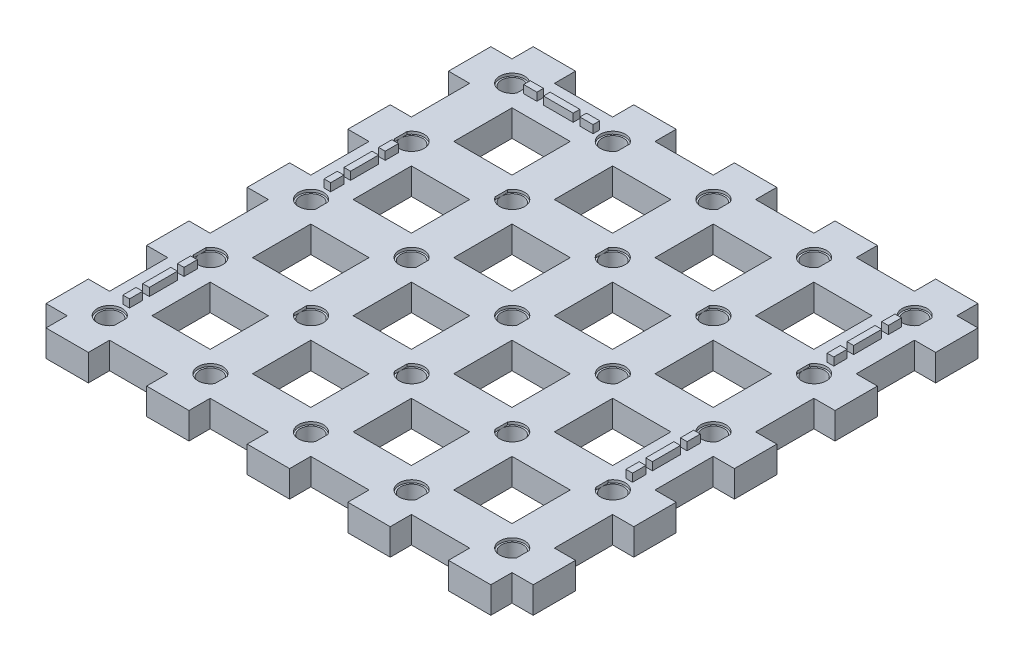
SolidWorks part; units mm, degrees
ref_plane "Front Plane" through (0, 0, 0) normal (0, 0, 1) x (1, 0, 0)
ref_plane "Top Plane" through (0, 0, 0) normal (0, 1, 0) x (1, 0, 0)
ref_plane "Right Plane" through (0, 0, 0) normal (1, 0, 0) x (0, 0, -1)
sketch "Sketch1" plane through (0, 0, 0) normal (0, 1, 0) x (1, 0, 0)
  line L1 (-110, -110) -> (110, -110)
  line L2 (-110, -110) -> (-110, 110)
  line L3 (-110, 110) -> (110, 110)
  line L4 (110, -110) -> (110, 110)
  line L5 (-110, -110) -> (110, 110) construction
  line L6 (-110, 110) -> (110, -110) construction
  point P0 (0, 0)
  dimension "D1" = 220
  dimension "D2" = 220
extrude "Boss-Extrude1" add sketch "Sketch1" along normal blind 10
sketch "Sketch2" plane through (0, 10, 0) normal (0, 1, 0) x (1, 0, 0)
  line L2 (-110, 110) -> (-110, -110) construction
  line L3 (-110, -110) -> (110, -110) construction
  circle A0 centre (-76, -75.925) radius 4.075
  circle A1 centre (-38, -75.925) radius 4.075
  circle A2 centre (0, -75.925) radius 4.075
  circle A3 centre (38, -75.925) radius 4.075
  circle A4 centre (76, -75.925) radius 4.075
  circle A5 centre (-76, -37.925) radius 4.075
  circle A6 centre (-38, -37.925) radius 4.075
  circle A7 centre (0, -37.925) radius 4.075
  circle A8 centre (38, -37.925) radius 4.075
  circle A9 centre (76, -37.925) radius 4.075
  circle A10 centre (-76, 0.075) radius 4.075
  circle A11 centre (-38, 0.075) radius 4.075
  circle A12 centre (0, 0.075) radius 4.075
  circle A13 centre (38, 0.075) radius 4.075
  circle A14 centre (76, 0.075) radius 4.075
  circle A15 centre (-76, 38.075) radius 4.075
  circle A16 centre (-38, 38.075) radius 4.075
  circle A17 centre (0, 38.075) radius 4.075
  circle A18 centre (38, 38.075) radius 4.075
  circle A19 centre (76, 38.075) radius 4.075
  circle A20 centre (-76, 76.075) radius 4.075
  circle A21 centre (-38, 76.075) radius 4.075
  circle A22 centre (0, 76.075) radius 4.075
  circle A23 centre (38, 76.075) radius 4.075
  circle A24 centre (76, 76.075) radius 4.075
  dimension "D1" = 8.15
  dimension "D5" = 38
  dimension "D7" = 38
  dimension "D2" = 30
  dimension "D3" = 34
  dimension "D4" = 5
  dimension "D6" = 5
extrude "Cut-Extrude1" cut sketch "Sketch2" against normal blind 10
sketch "Sketch3" plane through (0, 10, 0) normal (0, 1, 0) x (1, 0, 0)
  line L0 (-71.925, -78.2669) -> (-71.925, -73.5831)
  line L5 (-80.075, -35.5831) -> (-80.075, -40.2669)
  line L10 (-71.925, -2.2669) -> (-71.925, 2.4169)
  line L11 (-80.075, 40.4169) -> (-80.075, 35.7331)
  line L12 (-71.925, 73.7331) -> (-71.925, 78.4169)
  line L13 (-33.925, 73.7331) -> (-33.925, 78.4169)
  line L14 (-42.075, 40.4169) -> (-42.075, 35.7331)
  line L15 (-33.925, -2.2669) -> (-33.925, 2.4169)
  line L16 (-33.925, -78.2669) -> (-33.925, -73.5831)
  line L17 (-42.075, -35.5831) -> (-42.075, -40.2669)
  line L18 (4.075, 73.7331) -> (4.075, 78.4169)
  line L19 (-4.075, 40.4169) -> (-4.075, 35.7331)
  line L20 (4.075, -2.2669) -> (4.075, 2.4169)
  line L21 (4.075, -78.2669) -> (4.075, -73.5831)
  line L22 (-4.075, -35.5831) -> (-4.075, -40.2669)
  line L23 (42.075, 73.7331) -> (42.075, 78.4169)
  line L24 (33.925, 40.4169) -> (33.925, 35.7331)
  line L25 (42.075, -2.2669) -> (42.075, 2.4169)
  line L26 (42.075, -78.2669) -> (42.075, -73.5831)
  line L27 (33.925, -35.5831) -> (33.925, -40.2669)
  line L28 (80.075, 73.7331) -> (80.075, 78.4169)
  line L29 (71.925, 40.4169) -> (71.925, 35.7331)
  line L30 (80.075, -2.2669) -> (80.075, 2.4169)
  line L31 (80.075, -78.2669) -> (80.075, -73.5831)
  line L32 (71.925, -35.5831) -> (71.925, -40.2669)
  arc A0 (-71.925, -73.5831) -> (-71.925, -78.2669) centre (-76, -75.925) ccw
  circle A1 centre (-76, -75.925) radius 4.075 construction
  arc A6 (-80.075, -40.2669) -> (-80.075, -35.5831) centre (-76, -37.925) ccw
  circle A7 centre (-76, -37.925) radius 4.075 construction
  arc A12 (-71.925, 2.4169) -> (-71.925, -2.2669) centre (-76, 0.075) ccw
  arc A13 (-80.075, 35.7331) -> (-80.075, 40.4169) centre (-76, 38.075) ccw
  circle A14 centre (-76, 0.075) radius 4.075 construction
  circle A15 centre (-76, 38.075) radius 4.075 construction
  arc A16 (-71.925, 78.4169) -> (-71.925, 73.7331) centre (-76, 76.075) ccw
  circle A17 centre (-76, 76.075) radius 4.075 construction
  arc A18 (-33.925, 78.4169) -> (-33.925, 73.7331) centre (-38, 76.075) ccw
  arc A19 (-42.075, 35.7331) -> (-42.075, 40.4169) centre (-38, 38.075) ccw
  arc A20 (-33.925, 2.4169) -> (-33.925, -2.2669) centre (-38, 0.075) ccw
  arc A21 (-33.925, -73.5831) -> (-33.925, -78.2669) centre (-38, -75.925) ccw
  arc A22 (-42.075, -40.2669) -> (-42.075, -35.5831) centre (-38, -37.925) ccw
  arc A23 (4.075, 78.4169) -> (4.075, 73.7331) centre (0, 76.075) ccw
  arc A24 (-4.075, 35.7331) -> (-4.075, 40.4169) centre (0, 38.075) ccw
  arc A25 (4.075, 2.4169) -> (4.075, -2.2669) centre (0, 0.075) ccw
  arc A26 (4.075, -73.5831) -> (4.075, -78.2669) centre (0, -75.925) ccw
  arc A27 (-4.075, -40.2669) -> (-4.075, -35.5831) centre (0, -37.925) ccw
  arc A28 (42.075, 78.4169) -> (42.075, 73.7331) centre (38, 76.075) ccw
  arc A29 (33.925, 35.7331) -> (33.925, 40.4169) centre (38, 38.075) ccw
  arc A30 (42.075, 2.4169) -> (42.075, -2.2669) centre (38, 0.075) ccw
  arc A31 (42.075, -73.5831) -> (42.075, -78.2669) centre (38, -75.925) ccw
  arc A32 (33.925, -40.2669) -> (33.925, -35.5831) centre (38, -37.925) ccw
  arc A33 (80.075, 78.4169) -> (80.075, 73.7331) centre (76, 76.075) ccw
  arc A34 (71.925, 35.7331) -> (71.925, 40.4169) centre (76, 38.075) ccw
  arc A35 (80.075, 2.4169) -> (80.075, -2.2669) centre (76, 0.075) ccw
  arc A36 (80.075, -73.5831) -> (80.075, -78.2669) centre (76, -75.925) ccw
  arc A37 (71.925, -40.2669) -> (71.925, -35.5831) centre (76, -37.925) ccw
  point P0 (-76, -75.925)
  point P7 (-76, 76.075)
  point P11 (-76, 76.075)
  point P21 (-76, -37.925)
  point P26 (-76, -37.925)
  point P31 (-76, 38.075)
  point P51 (-76, 0.075)
  point P56 (-76, 38.075)
  point P60 (-76, 38.075)
  point P61 (-76, 0.075)
  point P102 (-38, -75.925)
  dimension "D1" = 4.7
  dimension "D3" = 4.7
  dimension "D5" = 4.7
  dimension "D6" = 4.7
  dimension "D2" = 4.7
extrude "Cut-Extrude2" cut sketch "Sketch3" against normal blind 1
sketch "Sketch4" plane through (0, 10, 0) normal (0, 1, 0) x (1, 0, 0)
  line L0 (-110, 110) -> (-110, -110) construction
  line L1 (-68, 46) -> (-46, 46)
  line L2 (-68, 46) -> (-68, 68)
  line L3 (-68, 68) -> (-46, 68)
  line L4 (-46, 46) -> (-46, 68)
  line L5 (-68, 46) -> (-46, 68) construction
  line L6 (-68, 68) -> (-46, 46) construction
  line L7 (110, 110) -> (-110, 110) construction
  line L8 (-30, 68) -> (-8, 68)
  line L9 (-30, 46) -> (-30, 68)
  line L10 (-30, 46) -> (-8, 46)
  line L11 (-8, 46) -> (-8, 68)
  line L12 (8, 68) -> (30, 68)
  line L13 (8, 46) -> (8, 68)
  line L14 (8, 46) -> (30, 46)
  line L15 (30, 46) -> (30, 68)
  line L16 (46, 68) -> (68, 68)
  line L17 (46, 46) -> (46, 68)
  line L18 (46, 46) -> (68, 46)
  line L19 (68, 46) -> (68, 68)
  line L20 (-30, 30) -> (-8, 30)
  line L21 (-30, 8) -> (-30, 30)
  line L22 (-30, 8) -> (-8, 8)
  line L23 (-8, 8) -> (-8, 30)
  line L24 (8, 30) -> (30, 30)
  line L25 (8, 8) -> (8, 30)
  line L26 (8, 8) -> (30, 8)
  line L27 (30, 8) -> (30, 30)
  line L28 (46, 30) -> (68, 30)
  line L29 (46, 8) -> (46, 30)
  line L30 (46, 8) -> (68, 8)
  line L31 (68, 8) -> (68, 30)
  line L32 (-68, 30) -> (-46, 30)
  line L33 (-68, 8) -> (-68, 30)
  line L34 (-68, 8) -> (-46, 8)
  line L35 (-46, 8) -> (-46, 30)
  line L36 (-30, -8) -> (-8, -8)
  line L37 (-30, -30) -> (-30, -8)
  line L38 (-30, -30) -> (-8, -30)
  line L39 (-8, -30) -> (-8, -8)
  line L40 (8, -8) -> (30, -8)
  line L41 (8, -30) -> (8, -8)
  line L42 (8, -30) -> (30, -30)
  line L43 (30, -30) -> (30, -8)
  line L44 (46, -8) -> (68, -8)
  line L45 (46, -30) -> (46, -8)
  line L46 (46, -30) -> (68, -30)
  line L47 (68, -30) -> (68, -8)
  line L48 (-68, -8) -> (-46, -8)
  line L49 (-68, -30) -> (-68, -8)
  line L50 (-68, -30) -> (-46, -30)
  line L51 (-46, -30) -> (-46, -8)
  line L52 (-30, -46) -> (-8, -46)
  line L53 (-30, -68) -> (-30, -46)
  line L54 (-30, -68) -> (-8, -68)
  line L55 (-8, -68) -> (-8, -46)
  line L56 (8, -46) -> (30, -46)
  line L57 (8, -68) -> (8, -46)
  line L58 (8, -68) -> (30, -68)
  line L59 (30, -68) -> (30, -46)
  line L60 (46, -46) -> (68, -46)
  line L61 (46, -68) -> (46, -46)
  line L62 (46, -68) -> (68, -68)
  line L63 (68, -68) -> (68, -46)
  line L64 (-68, -46) -> (-46, -46)
  line L65 (-68, -68) -> (-68, -46)
  line L66 (-68, -68) -> (-46, -68)
  line L67 (-46, -68) -> (-46, -46)
  line L68 (-68, 84) -> (-68, 92)
  line L76 (-84, 68) -> (-84, 46)
  line L109 (-46, 84) -> (-68, 84)
  line L158 (-92, 84) -> (-92, 68)
  line L177 (-84, 92) -> (-68, 92)
  line L194 (-92, 84) -> (-84, 84)
  line L195 (-92, 68) -> (-84, 68)
  line L196 (-84, 84) -> (-84, 92)
  line L197 (-92, 46) -> (-84, 46)
  line L198 (-92, 30) -> (-84, 30)
  line L201 (-92, 46) -> (-92, 30)
  line L202 (-84, 30) -> (-84, 8)
  line L203 (-92, 8) -> (-84, 8)
  line L204 (-92, -8) -> (-84, -8)
  line L205 (-92, 8) -> (-92, -8)
  line L206 (-84, -8) -> (-84, -30)
  line L207 (-92, -30) -> (-84, -30)
  line L208 (-92, -46) -> (-84, -46)
  line L209 (-46, 84) -> (-46, 92)
  line L210 (-46, 92) -> (-30, 92)
  line L211 (-30, 84) -> (-30, 92)
  line L212 (-8, 84) -> (-30, 84)
  line L213 (-8, 84) -> (-8, 92)
  line L214 (-8, 92) -> (8, 92)
  line L215 (8, 84) -> (8, 92)
  line L216 (30, 84) -> (8, 84)
  line L217 (30, 84) -> (30, 92)
  line L218 (30, 92) -> (46, 92)
  line L219 (46, 84) -> (46, 92)
  line L220 (68, 84) -> (46, 84)
  line L221 (0, -5.5) -> (0, 5.5) construction
  line L222 (-92, -30) -> (-92, -46)
  line L223 (-84, -46) -> (-84, -68)
  line L224 (-92, -68) -> (-84, -68)
  line L225 (-92, -84) -> (-84, -84)
  line L226 (-92, -68) -> (-92, -84)
  line L227 (-5.5, 0) -> (5.5, 0) construction
  line L228 (84, -84) -> (84, -92)
  line L229 (68, -92) -> (84, -92)
  line L230 (68, -84) -> (68, -92)
  line L231 (84, -84) -> (84, -92)
  line L232 (68, -84) -> (46, -84)
  line L233 (46, -84) -> (46, -92)
  line L234 (84, 84) -> (84, 92)
  line L235 (30, -92) -> (46, -92)
  line L236 (30, -84) -> (30, -92)
  line L237 (30, -84) -> (8, -84)
  line L238 (8, -84) -> (8, -92)
  line L239 (68, 84) -> (68, 92)
  line L240 (68, 92) -> (84, 92)
  line L241 (84, 84) -> (84, 92)
  line L242 (-8, -92) -> (8, -92)
  line L243 (-8, -84) -> (-8, -92)
  line L244 (-8, -84) -> (-30, -84)
  line L245 (-30, -84) -> (-30, -92)
  line L246 (-46, -92) -> (-30, -92)
  line L247 (-46, -84) -> (-46, -92)
  line L248 (-84, -84) -> (-84, -92)
  line L249 (-84, -92) -> (-68, -92)
  line L250 (-46, -84) -> (-68, -84)
  line L251 (92, 84) -> (92, 68)
  line L252 (-92, 46) -> (-92, 30) [skipped]
  line L253 (-92, 30) -> (-84, 30) [skipped]
  line L254 (-84, 30) -> (-84, 8) [skipped]
  line L255 (-92, 8) -> (-84, 8) [skipped]
  line L256 (-92, 8) -> (-92, -8) [skipped]
  line L257 (-92, -8) -> (-84, -8) [skipped]
  line L258 (-84, -8) -> (-84, -30) [skipped]
  line L259 (-92, -30) -> (-84, -30) [skipped]
  line L260 (-92, -30) -> (-92, -46) [skipped]
  line L261 (-92, -46) -> (-84, -46) [skipped]
  line L262 (-84, -46) -> (-84, -68) [skipped]
  line L263 (-92, -106) -> (-84, -106) [skipped]
  line L264 (-84, -84) -> (-84, -106) [skipped]
  line L265 (-68, -84) -> (-68, -92)
  line L266 (92, 68) -> (84, 68)
  line L267 (84, 68) -> (84, 46)
  line L268 (92, 46) -> (84, 46)
  line L269 (92, 46) -> (92, 30)
  line L270 (92, 30) -> (84, 30)
  line L271 (92, 8) -> (84, 8)
  line L272 (84, 30) -> (84, 8)
  line L273 (92, 8) -> (92, -8)
  line L274 (92, -8) -> (84, -8)
  line L275 (84, -8) -> (84, -30)
  line L276 (92, -30) -> (84, -30)
  line L277 (92, -30) -> (92, -46)
  line L278 (92, -46) -> (84, -46)
  line L279 (84, -46) -> (84, -68)
  line L280 (92, -68) -> (84, -68)
  line L281 (92, -68) -> (92, -84)
  line L282 (92, -84) -> (84, -84)
  line L283 (84, 84) -> (92, 84)
  line L285 (-110, 110) -> (110, 110)
  line L286 (-110, 110) -> (-110, -110)
  line L287 (-110, -110) -> (110, -110)
  line L288 (110, 110) -> (110, -110)
  point P0 (-57, 57)
  dimension "D2" = 22
  dimension "D3" = 22
  dimension "D4" = 53
  dimension "D6" = 16
  dimension "D8" = 16
  dimension "D9" = 16
  dimension "D10" = 26
  dimension "D11" = 26
  dimension "D12" = 4
  dimension "D14" = 53
  dimension "D19" = 8
  dimension "D20" = 8
  dimension "D5" = 4
  dimension "D7" = 4
  dimension "D15" = 5
extrude "Cut-Extrude3" cut sketch "Sketch4" against normal through all contours L62 L63 L60 L61 | L58 L59 L56 L57 | L54 L55 L52 L53 | L66 L67 L64 L65 | L50 L51 L48 L49 | L38 L39 L36 L37 | L42 L43 L40 L41 | L46 L47 L44 L45 | L30 L31 L28 L29 | L26 L27 L24 L25 | L22 L23 L20 L21 | L34 L35 L32 L33 | L1 L4 L3 L2 | L10 L11 L8 L9 | L14 L15 L12 L13 | L18 L19 L16 L17 | L288 L285 L286 L287 L234 L283 L251 L266 L267 L268 L269 L270 L272 L271 L273 L274 L275 L276 L277 L278 L279 L280 L281 L282 L228 L229 L230 L232 L233 L235 L236 L237 L238 L242 L243 L244 L245 L246 L247 L250 L265 L249 L248 L225 L226 L224 L223 L208 L222 L207 region at (-57, 10, -57) region at (-19, 10, -57) region at (19, 10, -57) region at (57, 10, -57) region at (-19, 10, -19) region at (19, 10, -19) region at (57, 10, -19) region at (-57, 10, -19) region at (-19, 10, 19) region at (19, 10, 19) region at (57, 10, 19) region at (-57, 10, 19) region at (-19, 10, 57) region at (19, 10, 57) region at (57, 10, 57) region at (-57, 10, 57) region at (0, 10, -106.8887)
sketch "Sketch5" plane through (0, 10, 0) normal (0, 1, 0) x (1, 0, 0)
  line L0 (-76, 76.075) -> (92, 76) construction
  line L2 (-71.925, 73.7331) -> (-71.925, 78.4169) construction
  line L11 (-70.425, 74.8214) -> (-65.425, 74.8214)
  line L12 (-70.425, 74.8214) -> (-70.425, 77.3214)
  line L13 (-70.425, 77.3214) -> (-65.425, 77.3214)
  line L14 (-65.425, 74.8214) -> (-65.425, 77.3214)
  line L15 (-70.425, 74.8214) -> (-65.425, 77.3214) construction
  line L16 (-70.425, 77.3214) -> (-65.425, 74.8214) construction
  line L17 (92, 84) -> (92, 68) construction
  line L18 (-49.2, 74.8214) -> (-44.2, 74.8214)
  line L19 (-49.2, 74.8214) -> (-49.2, 77.3214)
  line L20 (-49.2, 77.3214) -> (-44.2, 77.3214)
  line L21 (-44.2, 74.8214) -> (-44.2, 77.3214)
  line L22 (-49.2, 74.8214) -> (-44.2, 77.3214) construction
  line L23 (-49.2, 77.3214) -> (-44.2, 74.8214) construction
  line L24 (-62.925, 74.8119) -> (-51.7, 74.8119)
  line L25 (-62.925, 74.8119) -> (-62.925, 77.3214)
  line L26 (-62.925, 77.3214) -> (-51.7, 77.3214)
  line L27 (-51.7, 74.8119) -> (-51.7, 77.3214)
  line L28 (-62.925, 74.8119) -> (-51.7, 77.3214) construction
  line L29 (-62.925, 77.3214) -> (-51.7, 74.8119) construction
  line L33 (76, 76.075) -> (76, 37.6395) construction
  line L34 (-76, 38.075) -> (-76, 0) construction
  line L39 (74.75, 69.875) -> (77.25, 69.875)
  line L40 (74.75, 69.875) -> (74.75, 64.875)
  line L45 (74.75, 64.875) -> (77.25, 64.875)
  line L46 (77.25, 69.875) -> (77.25, 64.875)
  line L47 (74.75, 69.875) -> (77.25, 64.875) construction
  line L48 (74.75, 64.875) -> (77.25, 69.875) construction
  line L49 (74.75, 62.375) -> (77.25, 62.375)
  line L50 (74.75, 62.375) -> (74.75, 51.775)
  line L51 (74.75, 51.775) -> (77.25, 51.775)
  line L52 (77.25, 62.375) -> (77.25, 51.775)
  line L53 (74.75, 62.375) -> (77.25, 51.775) construction
  line L54 (74.75, 51.775) -> (77.25, 62.375) construction
  line L55 (74.75, 49.275) -> (77.25, 49.275)
  line L56 (74.75, 49.275) -> (74.75, 44.275)
  line L57 (74.75, 44.275) -> (77.25, 44.275)
  line L58 (77.25, 49.275) -> (77.25, 44.275)
  line L59 (74.75, 49.275) -> (77.25, 44.275) construction
  line L60 (74.75, 44.275) -> (77.25, 49.275) construction
  line L61 (-77.25, 31.875) -> (-74.75, 31.875)
  line L62 (-77.25, 31.875) -> (-77.25, 26.875)
  line L63 (-77.25, 26.875) -> (-74.75, 26.875)
  line L64 (-74.75, 31.875) -> (-74.75, 26.875)
  line L65 (-77.25, 31.875) -> (-74.75, 26.875) construction
  line L66 (-77.25, 26.875) -> (-74.75, 31.875) construction
  line L67 (-77.25, 24.375) -> (-74.75, 24.375)
  line L68 (-77.25, 24.375) -> (-77.25, 13.775)
  line L69 (-77.25, 13.775) -> (-74.75, 13.775)
  line L70 (-74.75, 24.375) -> (-74.75, 13.775)
  line L71 (-77.25, 24.375) -> (-74.75, 13.775) construction
  line L72 (-77.25, 13.775) -> (-74.75, 24.375) construction
  line L73 (-77.25, 11.275) -> (-74.75, 11.275)
  line L74 (-77.25, 11.275) -> (-77.25, 6.275)
  line L75 (-77.25, 6.275) -> (-74.75, 6.275)
  line L76 (-74.75, 11.275) -> (-74.75, 6.275)
  line L77 (-77.25, 11.275) -> (-74.75, 6.275) construction
  line L78 (-77.25, 6.275) -> (-74.75, 11.275) construction
  line L79 (-5.5, 0) -> (5.5, 0) construction
  line L80 (76, 0) -> (76, -37.925) construction
  line L81 (74.75, -6.125) -> (77.25, -6.125)
  line L82 (74.75, -6.125) -> (74.75, -11.125)
  line L83 (74.75, -11.125) -> (77.25, -11.125)
  line L84 (77.25, -6.125) -> (77.25, -11.125)
  line L85 (74.75, -6.125) -> (77.25, -11.125) construction
  line L86 (74.75, -11.125) -> (77.25, -6.125) construction
  line L87 (74.75, -13.625) -> (77.25, -13.625)
  line L88 (74.75, -13.625) -> (74.75, -24.225)
  line L89 (74.75, -24.225) -> (77.25, -24.225)
  line L90 (77.25, -13.625) -> (77.25, -24.225)
  line L91 (74.75, -13.625) -> (77.25, -24.225) construction
  line L92 (74.75, -24.225) -> (77.25, -13.625) construction
  line L93 (74.75, -26.725) -> (77.25, -26.725)
  line L94 (74.75, -26.725) -> (74.75, -31.725)
  line L95 (74.75, -31.725) -> (77.25, -31.725)
  line L96 (77.25, -26.725) -> (77.25, -31.725)
  line L97 (74.75, -26.725) -> (77.25, -31.725) construction
  line L98 (74.75, -31.725) -> (77.25, -26.725) construction
  line L99 (-76, -37.925) -> (-76, -76) construction
  line L100 (-77.25, -44.125) -> (-74.75, -44.125)
  line L101 (-77.25, -44.125) -> (-77.25, -49.125)
  line L102 (-77.25, -49.125) -> (-74.75, -49.125)
  line L103 (-74.75, -44.125) -> (-74.75, -49.125)
  line L104 (-77.25, -44.125) -> (-74.75, -49.125) construction
  line L105 (-77.25, -49.125) -> (-74.75, -44.125) construction
  line L106 (-77.25, -51.625) -> (-74.75, -51.625)
  line L107 (-77.25, -51.625) -> (-77.25, -62.225)
  line L108 (-77.25, -62.225) -> (-74.75, -62.225)
  line L109 (-74.75, -51.625) -> (-74.75, -62.225)
  line L110 (-77.25, -51.625) -> (-74.75, -62.225) construction
  line L111 (-77.25, -62.225) -> (-74.75, -51.625) construction
  line L112 (-77.25, -64.725) -> (-74.75, -64.725)
  line L113 (-77.25, -64.725) -> (-77.25, -69.725)
  line L114 (-77.25, -69.725) -> (-74.75, -69.725)
  line L115 (-74.75, -64.725) -> (-74.75, -69.725)
  line L116 (-77.25, -64.725) -> (-74.75, -69.725) construction
  line L117 (-77.25, -69.725) -> (-74.75, -64.725) construction
  arc A0 (-33.925, 78.4169) -> (-33.925, 73.7331) centre (-38, 76.075) ccw construction
  arc A2 (-80.075, -40.2669) -> (-80.075, -35.5831) centre (-76, -37.925) ccw construction
  arc A3 (80.075, 78.4169) -> (80.075, 73.7331) centre (76, 76.075) ccw construction
  arc A4 (71.925, 35.7331) -> (71.925, 40.4169) centre (76, 38.075) ccw construction
  arc A7 (-71.925, -73.5831) -> (-71.925, -78.2669) centre (-76, -75.925) ccw construction
  arc A8 (-80.075, 35.7331) -> (-80.075, 40.4169) centre (-76, 38.075) ccw construction
  arc A11 (-71.925, 2.4169) -> (-71.925, -2.2669) centre (-76, 0.075) ccw construction
  arc A12 (80.075, 2.4169) -> (80.075, -2.2669) centre (76, 0.075) ccw construction
  arc A13 (71.925, -40.2669) -> (71.925, -35.5831) centre (76, -37.925) ccw construction
  point P5 (-67.925, 76.0714)
  point P12 (-46.7, 76.0714)
  point P20 (-57.3125, 76.0667)
  point P26 (76, 67.375)
  point P32 (76, 57.075)
  point P37 (76, 46.775)
  point P41 (76, 76.075)
  point P52 (-76, 29.375)
  point P57 (-76, 19.075)
  point P62 (-76, 8.775)
  point P67 (-76, 38.075)
  point P68 (76, -37.925)
  point P70 (0, 0)
  point P81 (76, -8.625)
  point P86 (76, -18.925)
  point P91 (76, -29.225)
  point P96 (76, 0)
  point P97 (76, 0)
  point P98 (-76, -37.925)
  point P100 (0, 0)
  point P110 (-76, -46.625)
  point P115 (-76, -56.925)
  point P120 (-76, -67.225)
  point P125 (-76, -37.925)
  point P126 (-76, -37.925)
  dimension "D21" = 1.5
  dimension "D29" = 1.5
  dimension "D1" = 2.5
  dimension "D2" = 5
  dimension "D3" = 1.5
  dimension "D4" = 5
  dimension "D5" = 2.5
  dimension "D6" = 1.5
  dimension "D7" = 2.5
  dimension "D8" = 2.5
  dimension "D9" = 1.5
  dimension "D10" = 5
  dimension "D11" = 2.5
  dimension "D12" = 2.5
  dimension "D13" = 2.5
  dimension "D14" = 1.5
  dimension "D15" = 5
  dimension "D16" = 5
  dimension "D17" = 2.5
  dimension "D18" = 2.5
  dimension "D19" = 2.5
  dimension "D20" = 5
  dimension "D22" = 1.5
  dimension "D23" = 5
  dimension "D24" = 2.5
  dimension "D25" = 2.5
  dimension "D26" = 2.5
  dimension "D27" = 5
  dimension "D28" = 1.5
  dimension "D30" = 5
  dimension "D31" = 2.5
  dimension "D32" = 2.5
  dimension "D33" = 2.5
  dimension "D34" = 5
  dimension "D35" = 1.5
  dimension "D36" = 1.5
extrude "Boss-Extrude2" add sketch "Sketch5" along normal blind 3
sketch "Sketch6" plane through (0, 13, 0) normal (0, 1, 0) x (1, 0, 0)
  line L0 (-70.425, 76.0714) -> (-65.425, 76.0714) construction
  line L1 (-51.7, 74.8119) -> (-51.7, 77.3214) construction
  line L20 (-70.425, 77.3214) -> (-70.425, 74.8214) construction
  line L21 (-65.425, 74.8214) -> (-65.425, 77.3214) construction
  line L22 (-62.925, 76.0667) -> (-51.7, 76.0667) construction
  line L25 (-62.925, 74.8119) -> (-62.925, 77.3214) construction
  line L29 (-70.425, 75.7964) -> (-65.425, 75.7964)
  line L30 (-70.425, 75.7964) -> (-70.425, 76.3464)
  line L31 (-70.425, 76.3464) -> (-65.425, 76.3464)
  line L32 (-65.425, 75.7964) -> (-65.425, 76.3464)
  line L33 (-70.425, 75.7964) -> (-65.425, 76.3464) construction
  line L34 (-70.425, 76.3464) -> (-65.425, 75.7964) construction
  line L40 (-49.2, 76.0714) -> (-44.2, 76.0714) construction
  line L46 (-49.2, 74.8214) -> (-49.2, 77.3214) construction
  line L47 (-44.2, 74.8214) -> (-44.2, 77.3214) construction
  line L48 (-44.2, 74.8214) -> (-44.2, 77.3214) construction
  line L49 (-62.925, 75.5167) -> (-51.7, 75.5167)
  line L50 (-62.925, 75.5167) -> (-62.925, 76.6167)
  line L51 (-62.925, 76.6167) -> (-51.7, 76.6167)
  line L52 (-51.7, 75.5167) -> (-51.7, 76.6167)
  line L53 (-62.925, 75.5167) -> (-51.7, 76.6167) construction
  line L54 (-62.925, 76.6167) -> (-51.7, 75.5167) construction
  line L55 (-49.2, 75.7964) -> (-44.2, 75.7964)
  line L56 (-49.2, 75.7964) -> (-49.2, 76.3464)
  line L57 (-49.2, 76.3464) -> (-44.2, 76.3464)
  line L58 (-44.2, 75.7964) -> (-44.2, 76.3464)
  line L59 (-49.2, 75.7964) -> (-44.2, 76.3464) construction
  line L60 (-49.2, 76.3464) -> (-44.2, 75.7964) construction
  point P10 (-51.7, 76.0667)
  point P18 (-67.925, 76.0714)
  point P23 (-57.3125, 76.0667)
  point P28 (-46.7, 76.0714)
  point P35 (0, 0)
  point P36 (-52.014, 76.6167)
  point P37 (0, 0)
  point P39 (-51.7, 76.6167)
  dimension "D1" = 0.55
  dimension "D2" = 0.55
  dimension "D3" = 1.1
